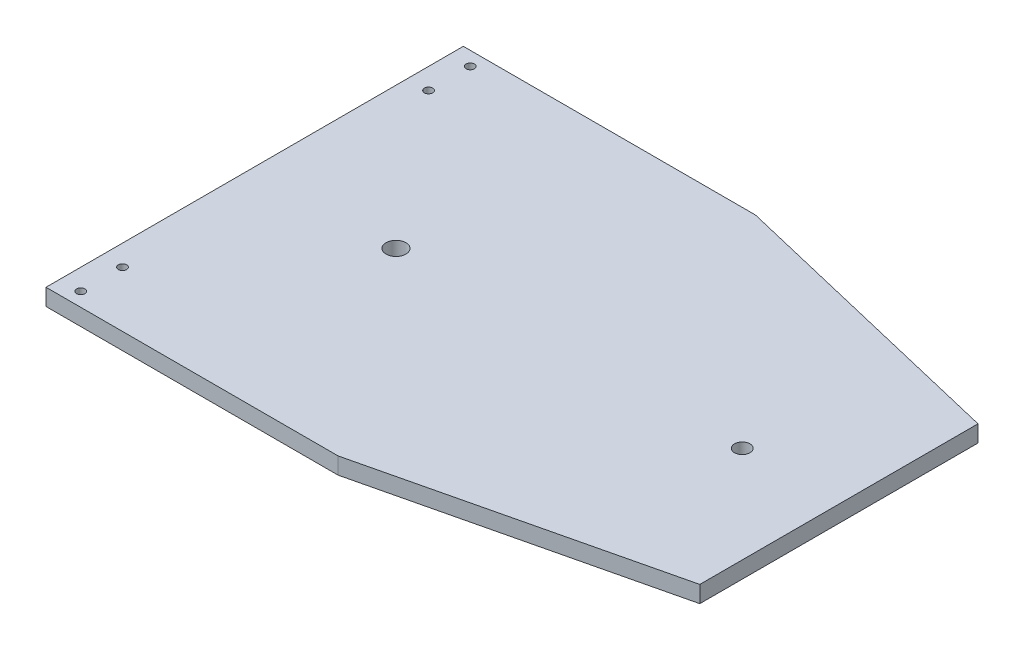
SolidWorks part; units mm, degrees
material "Carvalho"
ref_plane "Plano frontal" through (0, 0, 0) normal (0, 0, 1) x (1, 0, 0)
ref_plane "Plano superior" through (0, 0, 0) normal (0, 1, 0) x (1, 0, 0)
ref_plane "Plano direito" through (0, 0, 0) normal (1, 0, 0) x (0, 0, -1)
sketch "Esboço1" plane through (0, 0, 0) normal (0, 1, 0) x (1, 0, 0)
  line L0 (210, 50) -> (105, 75)
  line L1 (0, -75) -> (105, -75)
  line L2 (0, -75) -> (0, 75)
  line L3 (0, 75) -> (105, 75)
  line L4 (210, -50) -> (210, 50)
  line L7 (105, -75) -> (210, -50)
  line L8 (-14.8259, 0) -> (14.392, 0) construction
  line L9 (0, 21.2472) -> (0, -16.7598) construction
  circle A0 centre (50.8, 0) radius 3.5719
  circle A1 centre (175.26, 0) radius 2.7781
  circle A2 centre (7.5, -70) radius 1.5
  circle A3 centre (7.5, -55) radius 1.5
  circle A4 centre (7.5, 55) radius 1.5
  circle A5 centre (7.5, 70) radius 1.5
  point P0 (0, 0)
  dimension "D3" = 7.1437
  dimension "D5" = 5.5562
  dimension "D1" = 25
  dimension "D2" = 150
  dimension "D4" = 50.8
  dimension "D6" = 210
  dimension "D7" = 175.26
  dimension "D8" = 105
extrude "Ressalto-extrusão1" add sketch "Esboço1" along normal blind 6
